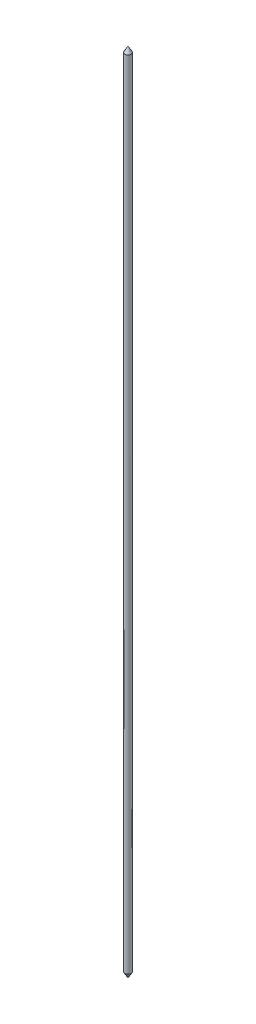
SolidWorks part; units mm, degrees
ref_plane "Alzado" through (0, 0, 0) normal (0, 0, 1) x (1, 0, 0)
ref_plane "Planta" through (0, 0, 0) normal (0, 1, 0) x (1, 0, 0)
ref_plane "Vista lateral" through (0, 0, 0) normal (1, 0, 0) x (0, 0, -1)
sketch "Croquis1" plane through (0, 0, 0) normal (0, 1, 0) x (1, 0, 0)
  circle A0 centre (0, 0) radius 1
  dimension "D1" = 2
extrude "Saliente-Extruir1" add sketch "Croquis1" along normal blind 250
ref_axis "Eje1" through (0, 250, 0) along (0, -1, 0)
sketch "Croquis2" plane through (0, 250, 0) normal (0, 1, 0) x (1, 0, 0)
  circle A0 centre (0, 0) radius 1
  dimension "D1" = 2
extrude "Saliente-Extruir2" add sketch "Croquis2" along normal blind 50 draft 30
sketch "Croquis3" plane through (0, 0, 0) normal (0, -1, 0) x (1, 0, 0)
  circle A0 centre (0, 0) radius 1
  dimension "D1" = 2
extrude "Saliente-Extruir3" add sketch "Croquis3" along normal blind 50 draft 30
